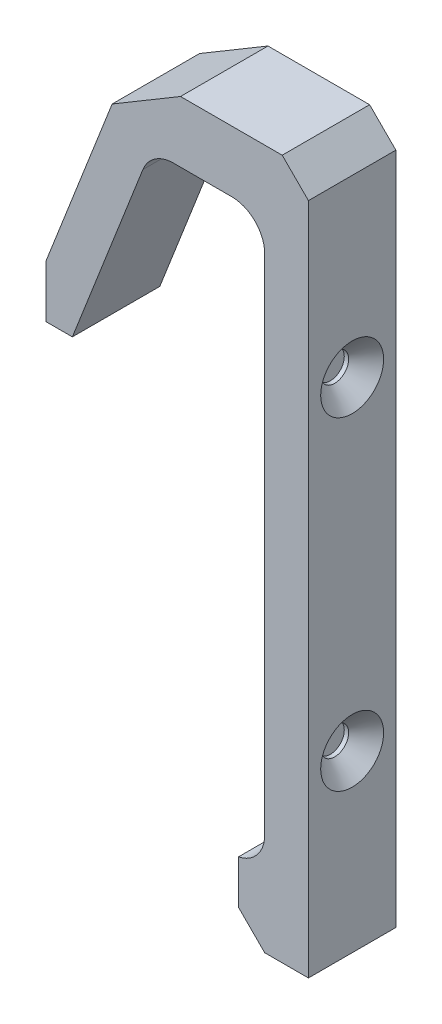
SolidWorks part; units mm, degrees
material "1060 Alloy"
ref_plane "Front Plane" through (0, 0, 0) normal (0, 0, 1) x (1, 0, 0)
ref_plane "Top Plane" through (0, 0, 0) normal (0, 1, 0) x (1, 0, 0)
ref_plane "Right Plane" through (0, 0, 0) normal (1, 0, 0) x (0, 0, -1)
sketch "Sketch1" plane through (0, 0, 0) normal (0, 0, 1) x (1, 0, 0)
  line L1 (0, 0) -> (76.2, 0)
  line L2 (0, 0) -> (0, 203.2)
  line L3 (0, 203.2) -> (76.2, 203.2)
  line L4 (76.2, 0) -> (76.2, 203.2)
  dimension "D1" = 76.2
  dimension "D2" = 203.2
extrude "Boss-Extrude1" add sketch "Sketch1" along normal blind 25.4
sketch "Sketch2" plane through (0, 0, 25.4) normal (0, 0, 1) x (1, 0, 0)
  line L1 (0, 0) -> (55.88, 0)
  line L2 (0, 0) -> (0, 127)
  line L3 (0, 127) -> (7.62, 127)
  line L6 (63.5, 20.32) -> (63.5, 185.42)
  line L7 (63.5, 185.42) -> (30.48, 185.42)
  line L8 (7.62, 127) -> (30.48, 185.42)
  line L9 (63.5, 20.32) -> (55.88, 20.32)
  line L10 (0, 142.3785) -> (23.7997, 203.2)
  line L11 (0, 203.2) -> (0, 0) construction
  line L12 (76.2, 203.2) -> (0, 203.2) construction
  line L13 (23.7997, 203.2) -> (0, 203.2)
  line L14 (0, 203.2) -> (0, 142.3785)
  line L15 (76.2, 0) -> (76.2, 203.2) construction
  line L16 (55.88, 0) -> (55.88, 20.32)
  dimension "D1" = 12.7
  dimension "D2" = 17.78
  dimension "D3" = 12.7
  dimension "D4" = 33.02
  dimension "D5" = 55.88
  dimension "D6" = 76.2
  dimension "D7" = 7.62
  dimension "D8" = 20.32
extrude "Cut-Extrude1" cut sketch "Sketch2" against normal through all
fillet "Fillet1" radius 9.525 2 edges at (30.48, 185.42, 12.7) (63.5, 185.42, 12.7)
chamfer "Chamfer3" distance 7.62 angle 45 1 edges at (76.2, 203.2, 12.7)
chamfer "Chamfer5" distance 12.7 distance2 15.24 1 edges at (23.7997, 203.2, 12.7) first distance on face at (11.8999, 172.7893, 12.7)
sketch "Sketch5" plane through (76.2, 0, 0) normal (1, 0, 0) x (0, 0, -1)
  line L0 (-12.7, 195.58) -> (-12.7, 0) construction
  line L1 (0, 195.58) -> (-25.4, 195.58) construction
  line L2 (-25.4, 0) -> (0, 0) construction
  circle A0 centre (-12.7, 144.78) radius 4.064
  circle A1 centre (-12.7, 50.8) radius 4.064
  dimension "D3" = 8.128
  dimension "D1" = 50.8
  dimension "D2" = 50.8
extrude "Cut-Extrude2" cut sketch "Sketch5" against normal blind 6.35
chamfer "Chamfer6" distance 5.08 angle 45 2 edges at (76.2, 50.8, 8.636) (76.2, 144.78, 8.636)
fillet "Fillet2" radius 9.525 1 edges at (63.5, 20.32, 12.7)
chamfer "Chamfer7" distance 7.62 angle 45 1 edges at (55.88, 0, 12.7)
